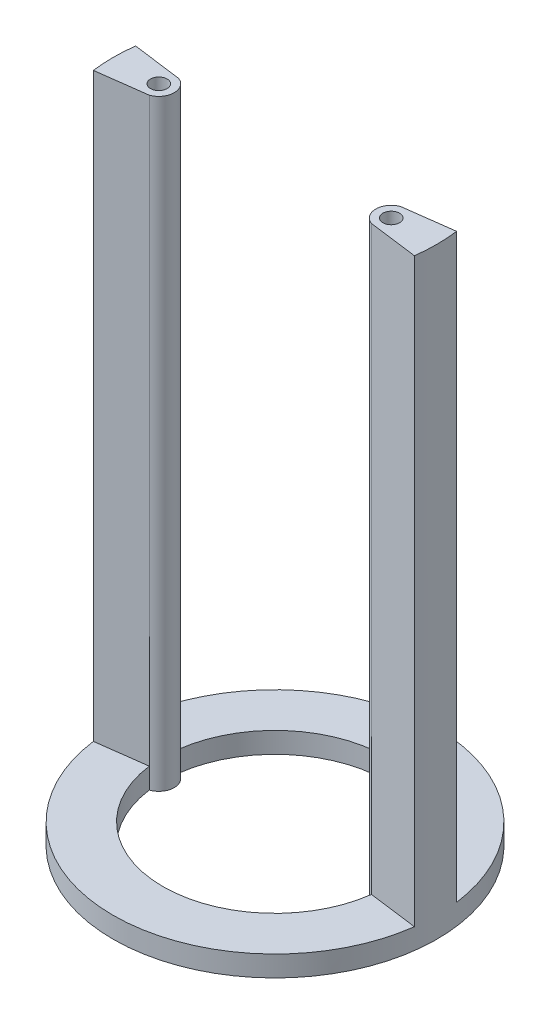
SolidWorks part; units mm, degrees
ref_plane "Front Plane" through (0, 0, 0) normal (0, 0, 1) x (1, 0, 0)
ref_plane "Top Plane" through (0, 0, 0) normal (0, 1, 0) x (1, 0, 0)
ref_plane "Right Plane" through (0, 0, 0) normal (1, 0, 0) x (0, 0, -1)
sketch "Sketch1" plane through (0, 0, 0) normal (0, 1, 0) x (1, 0, 0)
  circle A0 centre (0, 0) radius 49.53
  circle A1 centre (0, 0) radius 34.29
  dimension "D1" = 99.06
extrude "Boss-Extrude1" add sketch "Sketch1" along normal blind 6.35
sketch "Sketch2" plane through (0, 6.35, 0) normal (0, 1, 0) x (1, 0, 0)
  line L0 (-3.4925, 0) -> (3.4925, 0) construction
  line L1 (0, -3.4925) -> (0, 3.4925) construction
  line L2 (-49.1063, 6.465) -> (-33.9966, 4.4757)
  line L3 (-33.9966, -4.4757) -> (-49.1063, -6.465)
  line L4 (33.9966, 4.4757) -> (49.1063, 6.465)
  line L5 (33.9966, -4.4757) -> (49.1063, -6.465)
  arc A0 (-49.1063, -6.465) -> (-49.1063, 6.465) centre (0, 0) cw
  arc A2 (49.1063, -6.465) -> (49.1063, 6.465) centre (0, 0) ccw
  circle A4 centre (0, 0) radius 34.29 construction
  circle A6 centre (-35.56, 0) radius 2.5527
  arc A7 (-33.9966, -4.4757) -> (-33.9966, 4.4757) centre (-35.56, 0) ccw
  arc A8 (33.9966, -4.4757) -> (33.9966, 4.4757) centre (35.56, 0) cw
  circle A9 centre (35.56, 0) radius 2.5527
  dimension "D1" = 35.56
extrude "Boss-Extrude2" add sketch "Sketch2" along normal blind 177.8
sketch "Sketch5" plane through (0, 0, 0) normal (0, -1, 0) x (1, 0, 0)
  line L2 (-49.1063, 6.465) -> (-33.9966, 4.4757)
  line L3 (-33.9966, -4.4757) -> (-49.1063, -6.465)
  line L4 (33.9966, 4.4757) -> (49.1063, 6.465)
  line L5 (33.9966, -4.4757) -> (49.1063, -6.465)
  arc A0 (-49.1063, -6.465) -> (-49.1063, 6.465) centre (0, 0) cw
  arc A2 (49.1063, -6.465) -> (49.1063, 6.465) centre (0, 0) ccw
  circle A6 centre (-35.56, 0) radius 2.5527
  arc A7 (-33.9966, -4.4757) -> (-33.9966, 4.4757) centre (-35.56, 0) ccw
  arc A8 (33.9966, -4.4757) -> (33.9966, 4.4757) centre (35.56, 0) cw
  circle A9 centre (35.56, 0) radius 2.5527
  dimension "D1" = 35.56
extrude "Cut-Extrude1" cut sketch "Sketch5" against normal blind 6.35 contours A9 | A6
extrude "Boss-Extrude3" add sketch "Sketch2<3>" against normal blind 6.35
sketch "Sketch2<3>" plane through (0, 6.35, 0) normal (0, 1, 0) x (1, 0, 0) same geometry as "Sketch2"
